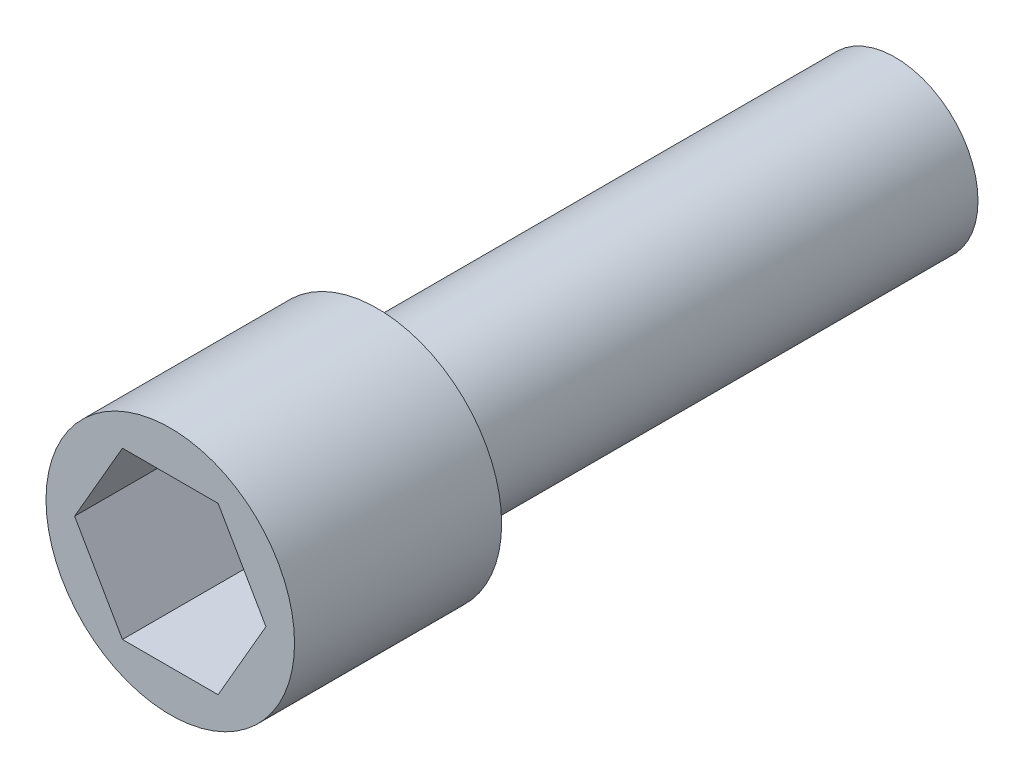
SolidWorks part; units mm, degrees
material "AISI 304"
ref_plane "Front Plane" through (0, 0, 0) normal (0, 0, 1) x (1, 0, 0)
ref_plane "Top Plane" through (0, 0, 0) normal (0, 1, 0) x (1, 0, 0)
ref_plane "Right Plane" through (0, 0, 0) normal (1, 0, 0) x (0, 0, -1)
sketch "Sketch1" plane through (0, 0, 0) normal (0, 0, 1) x (1, 0, 0)
  line L1 (4.6188, 0) -> (2.3094, 4)
  line L2 (2.3094, 4) -> (-2.3094, 4)
  line L3 (-2.3094, 4) -> (-4.6188, 0)
  line L4 (-4.6188, 0) -> (-2.3094, -4)
  line L5 (-2.3094, -4) -> (2.3094, -4)
  line L6 (2.3094, -4) -> (4.6188, 0)
  circle A0 centre (0, 0) radius 4
  circle A1 centre (0, 0) radius 6
  circle A2 centre (0, 0) radius 4 construction
  dimension "D1" = 12
  dimension "D3" = 8
  dimension "D2" = 8
extrude "Boss-Extrude1" add sketch "Sketch1" against normal blind 10 contours A1
extrude "Boss-Extrude2" add sketch "Sketch1<3>" against normal blind 35 contours A0
sketch "Sketch1<3>" plane through (0, 0, 0) normal (0, 0, 1) x (1, 0, 0) same geometry as "Sketch1"
extrude "Cut-Extrude1" cut sketch "Sketch1<4>" against normal blind 7 contours L2 L3 L4 L5 L6 L1
sketch "Sketch1<4>" plane through (0, 0, 0) normal (0, 0, 1) x (1, 0, 0) same geometry as "Sketch1"
